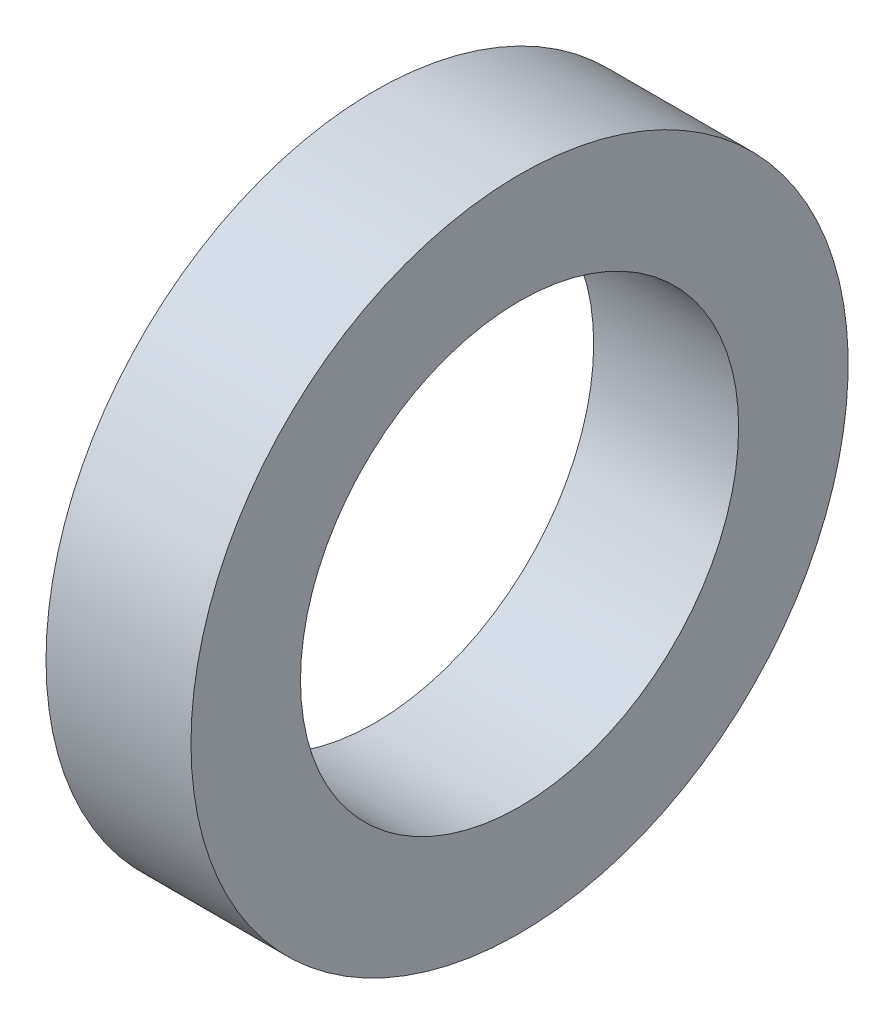
SolidWorks part; units mm, degrees
ref_plane "Front Plane" through (0, 0, 0) normal (0, 0, 1) x (1, 0, 0)
ref_plane "Top Plane" through (0, 0, 0) normal (0, 1, 0) x (1, 0, 0)
ref_plane "Right Plane" through (0, 0, 0) normal (1, 0, 0) x (0, 0, -1)
sketch "Sketch2" plane through (0, 0, 0) normal (0, 0, 1) x (1, 0, 0)
  line L0 (0, 0) -> (58.591, 0) construction
  line L2 (0, 0) -> (18.4, 0)
  line L3 (0, 0) -> (0, 2.5)
  line L4 (0, 2.5) -> (18.4, 2.5)
  line L5 (18.4, 0) -> (18.4, 2.5)
  line L6 (6.0094, 2.5) -> (6.0094, 6)
  line L11 (6.0094, 6) -> (9.9794, 6)
  line L16 (12.9794, 6) -> (12.9794, 3)
  line L17 (12.9794, 3) -> (13.6398, 3)
  line L18 (13.6398, 3) -> (13.6398, 2.5)
  line L19 (13.6398, 2.5) -> (6.0094, 2.5)
  line L22 (13.6398, 2.5) -> (16.1198, 2.5)
  line L23 (13.6398, 2.5) -> (13.6398, 4)
  line L24 (13.6398, 4) -> (16.1198, 4)
  line L25 (16.1198, 2.5) -> (16.1198, 4)
  line L27 (6.0094, 6) -> (9.9794, 6)
  line L28 (6.0094, 6) -> (6.0094, 9)
  line L29 (6.0094, 9) -> (9.9794, 9)
  line L30 (9.9794, 6) -> (9.9794, 9)
  line L31 (6.0094, 9) -> (6.0094, 8.25)
  line L32 (6.0094, 8.25) -> (5.0094, 8.25)
  line L33 (8.6609, 22.001) -> (8.6609, 12.476) construction
  line L34 (5.0094, 12.476) -> (12.3124, 12.476)
  line L35 (9.9794, 9) -> (12.3124, 9)
  line L36 (5.0094, 7.9375) -> (1.8344, 7.9375)
  line L37 (5.0094, 8.25) -> (5.0094, 12.476)
  line L38 (5.0094, 7.9375) -> (5.0094, 13.9365)
  line L39 (5.0094, 13.9365) -> (1.8344, 13.9365)
  line L40 (1.8344, 7.9375) -> (1.8344, 13.9365)
  line L41 (5.0094, 22.001) -> (12.3124, 22.001)
  line L42 (5.0094, 22.001) -> (5.0094, 30.1625)
  line L43 (5.0094, 30.1625) -> (12.3124, 30.1625)
  line L44 (12.3124, 22.001) -> (12.3124, 30.1625)
  line L49 (16.6398, 22.001) -> (16.6398, 7.5)
  line L51 (23.0198, 7.5) -> (23.0198, 6.5)
  line L54 (16.1198, 4) -> (13.6398, 4)
  line L56 (18.0398, 7.5) -> (23.0198, 7.5)
  line L57 (13.3124, 22.001) -> (16.6398, 22.001)
  line L58 (16.1198, 3.5) -> (20.0198, 3.5)
  line L59 (29.9098, 14) -> (26.9098, 11)
  line L60 (4.0094, 31.75) -> (18.0398, 31.75)
  line L61 (18.0398, 7.5) -> (23.0198, 7.5)
  line L62 (18.0398, 7.5) -> (18.0398, 12)
  line L63 (18.0398, 12) -> (23.0198, 12)
  line L64 (23.0198, 7.5) -> (23.0198, 12)
  line L65 (18.0398, 31.75) -> (18.0398, 12)
  line L66 (23.0198, 11) -> (26.9098, 11)
  line L67 (34.8098, 23) -> (31.3098, 19.5)
  line L68 (35.8098, 31) -> (38.7998, 33.99)
  line L69 (29.9098, 14) -> (29.9098, 15)
  line L70 (29.9098, 15) -> (22.9398, 15)
  line L71 (22.9398, 15) -> (21.0398, 15)
  line L72 (18.0398, 7.5) -> (16.6398, 7.5)
  line L73 (21.0398, 15) -> (21.0398, 43)
  line L74 (19.5798, 40) -> (9.6198, 40)
  line L75 (9.6198, 40) -> (4.0094, 40)
  line L76 (21.0398, 43) -> (19.5798, 43)
  line L77 (22.9398, 15) -> (29.9098, 15)
  line L78 (22.9398, 15) -> (22.9398, 21)
  line L79 (22.9398, 21) -> (29.9098, 21)
  line L80 (29.9098, 15) -> (29.9098, 21)
  line L81 (9.6198, 40) -> (19.5798, 40)
  line L82 (9.6198, 40) -> (9.6198, 50)
  line L83 (9.6198, 50) -> (19.5798, 50)
  line L84 (19.5798, 40) -> (19.5798, 50)
  line L85 (4.0094, 40) -> (4.0094, 31.75)
  line L86 (12.9794, 3) -> (12.9794, 2.5)
  line L87 (31.3098, 19.5) -> (29.9098, 19.5)
  line L88 (21.4694, 63.5) -> (21.4694, 51.308)
  line L89 (21.4694, 63.5) -> (25.9398, 63.5)
  line L90 (25.9398, 63.5) -> (25.9398, 25)
  line L91 (27.8398, 25) -> (25.9398, 25)
  line L92 (9.6198, 48) -> (8.1598, 48)
  line L93 (8.1598, 48) -> (8.1598, 53.476)
  line L94 (8.1598, 53.476) -> (19.5798, 53.476)
  line L95 (19.5798, 53.476) -> (19.5798, 50)
  line L96 (13.8698, 63.001) -> (13.8698, 53.476) construction
  line L97 (8.1598, 63.001) -> (19.5798, 63.001)
  line L98 (8.1598, 63.001) -> (8.1598, 68.2625)
  line L99 (8.1598, 68.2625) -> (19.5798, 68.2625)
  line L100 (19.5798, 63.001) -> (19.5798, 68.2625)
  line L101 (12.9794, 6) -> (11.9794, 6)
  line L102 (8.1598, 44.825) -> (4.9848, 44.825)
  line L103 (8.1598, 44.825) -> (8.1598, 54.9365)
  line L104 (8.1598, 54.9365) -> (4.9848, 54.9365)
  line L106 (9.9794, 6) -> (10.8794, 6)
  line L107 (27.8398, 25) -> (34.8098, 25)
  line L108 (34.8098, 25) -> (34.8098, 23)
  line L109 (0, 0) -> (-2, 0)
  line L110 (0, 0) -> (0, 11)
  line L111 (27.8398, 25) -> (34.8098, 25)
  line L112 (27.8398, 25) -> (27.8398, 32.5)
  line L113 (27.8398, 32.5) -> (34.8098, 32.5)
  line L114 (34.8098, 25) -> (34.8098, 32.5)
  line L115 (35.8098, 31) -> (34.8098, 31)
  line L116 (27.8398, 32.5) -> (27.8398, 64.5)
  line L117 (20.5373, 74.025) -> (6.2023, 74.025)
  line L118 (6.2023, 74.025) -> (6.2023, 76.2)
  line L119 (38.7998, 47.29) -> (30.8398, 55.25)
  line L120 (0, 11) -> (-2, 11)
  line L121 (38.7998, 43.815) -> (30.8623, 43.815)
  line L123 (-4.8152, 69.85) -> (1.5348, 76.2)
  line L124 (38.7998, 47.29) -> (38.7998, 33.99)
  line L125 (-2, 0) -> (-2, 11)
  line L126 (38.7998, 37.465) -> (30.8623, 37.465)
  line L127 (30.8623, 43.815) -> (30.8623, 37.465)
  line L128 (6.0094, 2.5) -> (6.0094, 0)
  line L129 (-0.0152, 63.5) -> (-0.0152, 30)
  line L132 (4.9848, 63.5) -> (-0.0152, 63.5)
  line L136 (-1.8152, 30) -> (-11.7752, 30)
  line L138 (-13.7752, 25.4) -> (-2, 25.4)
  line L139 (-2, 25.4) -> (-2, 11.5)
  line L140 (27.8398, 64.5) -> (20.5373, 64.5)
  line L141 (-1.8152, 30) -> (-11.7752, 30)
  line L142 (-1.8152, 30) -> (-1.8152, 39)
  line L143 (-1.8152, 39) -> (-11.7752, 39)
  line L144 (-11.7752, 30) -> (-11.7752, 39)
  line L145 (20.5373, 64.5) -> (20.5373, 74.025)
  line L146 (-12.7752, 37) -> (-12.7752, 47.29)
  line L147 (-12.7752, 37) -> (-11.7752, 37)
  line L148 (30.8398, 55.25) -> (30.8398, 76.2)
  line L149 (11.9794, 6) -> (11.9794, 5.45)
  line L154 (-2, 11.5) -> (0.5, 11.5)
  line L155 (4.9848, 60.6197) -> (24.0348, 60.6197)
  line L160 (4.9848, 60.6197) -> (4.9848, 55.8572)
  line L161 (4.9848, 55.8572) -> (24.0348, 55.8572)
  line L166 (24.0348, 60.6197) -> (24.0348, 55.8572)
  line L167 (4.9848, 60.6197) -> (24.0348, 55.8572) construction
  line L172 (4.9848, 55.8572) -> (24.0348, 60.6197) construction
  line L173 (24.0348, 62.2072) -> (25.9398, 62.2072)
  line L174 (11.9794, 5.45) -> (10.8794, 5.45)
  line L175 (10.8794, 6) -> (10.8794, 5.45)
  line L176 (24.0348, 62.2072) -> (24.0348, 54.2697)
  line L177 (24.0348, 54.2697) -> (25.9398, 54.2697)
  line L178 (25.9398, 62.2072) -> (25.9398, 54.2697)
  line L179 (24.0348, 62.2072) -> (25.9398, 54.2697) construction
  line L180 (24.0348, 54.2697) -> (25.9398, 62.2072) construction
  line L181 (3, 19.6197) -> (15.7, 19.6197)
  line L182 (3, 19.6197) -> (3, 14.8572)
  line L183 (3, 14.8572) -> (15.7, 14.8572)
  line L184 (15.7, 19.6197) -> (15.7, 14.8572)
  line L185 (3, 19.6197) -> (15.7, 14.8572) construction
  line L186 (3, 14.8572) -> (15.7, 19.6197) construction
  line L187 (15.7, 21.2072) -> (16.6398, 21.2072)
  line L188 (15.7, 21.2072) -> (15.7, 13.2697)
  line L189 (15.7, 13.2697) -> (16.6398, 13.2697)
  line L190 (16.6398, 21.2072) -> (16.6398, 13.2697)
  line L191 (15.7, 21.2072) -> (16.6398, 13.2697) construction
  line L192 (15.7, 13.2697) -> (16.6398, 21.2072) construction
  line L193 (0.5, 11.5) -> (0.5, 6.9375)
  line L194 (0.5, 6.9375) -> (1.8344, 6.9375)
  line L195 (23.0198, 6.5) -> (20.0198, 3.5)
  line L196 (4.9848, 63.5) -> (4.9848, 54.9365)
  line L197 (3, 43.825) -> (4.9848, 43.825)
  line L198 (1.8344, 6.9375) -> (1.8344, 7.9375)
  line L199 (6.0094, 0) -> (12.9794, 0)
  line L200 (12.9794, 0) -> (12.9794, 2.5)
  line L201 (18.0398, 31.75) -> (18.0398, 35.875)
  line L202 (18.0398, 35.875) -> (21.0398, 35.875)
  line L203 (30.8398, 76.2) -> (6.2023, 76.2)
  line L204 (2.7573, 69.85) -> (7.2023, 69.85) construction
  line L205 (7.2023, 67.4688) -> (26.2523, 67.4688)
  line L206 (7.2023, 74.025) -> (7.2023, 64.5)
  line L207 (7.2023, 64.5) -> (-1.8152, 64.5)
  line L208 (-1.8152, 64.5) -> (-1.8152, 39)
  line L209 (-12.7752, 47.29) -> (-4.8152, 55.25)
  line L210 (-4.8152, 55.25) -> (-4.8152, 69.85)
  line L211 (7.2023, 67.4688) -> (7.2023, 72.2312)
  line L212 (7.2023, 72.2312) -> (26.2523, 72.2313)
  line L213 (26.2523, 67.4688) -> (26.2523, 72.2313)
  line L214 (26.2523, 73.8187) -> (30.8398, 73.8187)
  line L215 (26.2523, 73.8187) -> (26.2523, 65.8813)
  line L216 (26.2523, 65.8813) -> (30.8398, 65.8813)
  line L217 (30.8398, 73.8187) -> (30.8398, 65.8813)
  line L218 (2.7573, 72.2313) -> (24.9823, 72.2313)
  line L219 (2.7573, 72.2313) -> (2.7573, 67.4687)
  line L220 (2.7573, 67.4687) -> (24.9823, 67.4687)
  line L221 (24.9823, 72.2313) -> (24.9823, 67.4687)
  line L222 (24.9823, 69.85) -> (20.5373, 69.85) construction
  line L223 (21.4694, 51.308) -> (22.9398, 51.308)
  line L224 (22.9398, 51.308) -> (22.9398, 21)
  line L225 (13.6398, 4) -> (13.6398, 12.2697)
  line L226 (13.6398, 12.2697) -> (13.3124, 12.2697)
  line L227 (13.3124, 12.2697) -> (13.3124, 22.001)
  line L228 (12.3124, 9) -> (12.3124, 12.476)
  line L229 (-1.8152, 30) -> (-0.0152, 30)
  line L230 (8.1598, 65.6317) -> (2.7573, 65.6317) construction
  line L231 (19.5798, 65.6317) -> (24.9823, 65.6317) construction
  line L232 (1.5348, 76.2) -> (6.2023, 76.2)
  line L233 (-11.7752, 30) -> (-13.7752, 30)
  line L234 (-13.7752, 30) -> (-13.7752, 25.4)
  line L235 (3, 13.9365) -> (3, 43.825)
  line L236 (4.9848, 54.9365) -> (4.9848, 44.825)
  line L237 (4.9848, 43.825) -> (4.9848, 44.825)
  circle A0 centre (26.8898, 25.95) radius 0.95
  circle A1 centre (21.9898, 15.95) radius 0.95
  circle A2 centre (17.3398, 8.2) radius 0.7
  circle A3 centre (10.4294, 6.45) radius 0.45
  circle A4 centre (-0.9152, 30.9) radius 0.9
  point P7 (24.9873, 58.2385)
  point P131 (16.1699, 17.2385)
  point P135 (14.5098, 58.2385)
  point P146 (9.35, 17.2385)
sketch "Sketch3" plane through (0, 0, 0) normal (0, 0, 1) x (1, 0, 0)
  line L0 (6.0094, 9) -> (9.9794, 9) construction
  line L1 (9.9794, 6) -> (9.9794, 9) construction
  line L2 (6.0094, 6) -> (9.9794, 6) construction
  line L3 (6.0094, 6) -> (6.0094, 9) construction
  line L4 (6.0094, 9) -> (9.9794, 9)
  line L5 (9.9794, 6) -> (9.9794, 9)
  line L6 (6.0094, 6) -> (9.9794, 6)
  line L7 (6.0094, 6) -> (6.0094, 9)
revolve "Revolve1" add sketch "Sketch3" angle 360 about L0
